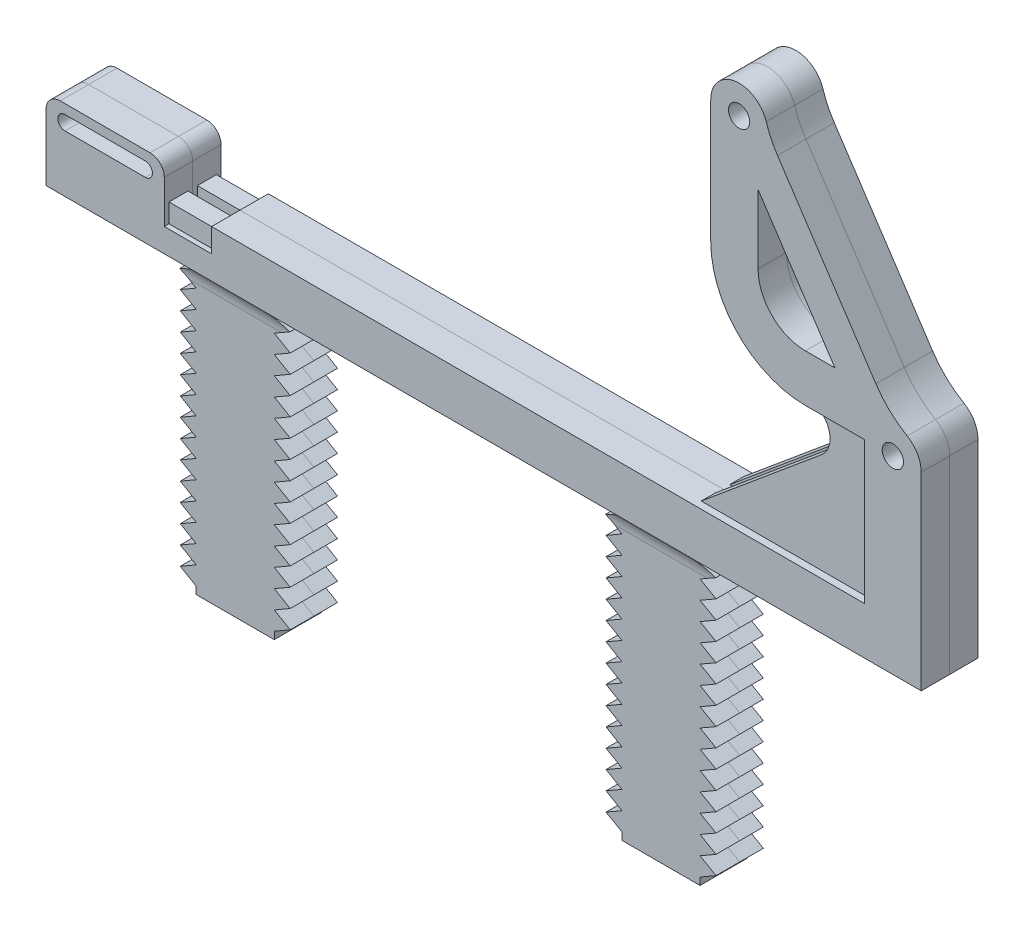
SolidWorks part; units mm, degrees
ref_plane "Front Plane" through (0, 0, 0) normal (0, 0, 1) x (1, 0, 0)
ref_plane "Top Plane" through (0, 0, 0) normal (0, 1, 0) x (1, 0, 0)
ref_plane "Right Plane" through (0, 0, 0) normal (1, 0, 0) x (0, 0, -1)
sketch "Sketch1" plane through (0, 0, 0) normal (0, 0, 1) x (1, 0, 0)
  line L0 (0, 0) -> (-32.49, 0) construction
  line L1 (-6, 0) -> (6, 0) construction
  line L2 (-6, 0) -> (-6, -40)
  line L3 (-6, -40) -> (6, -40)
  line L4 (6, 0) -> (6, -40)
  line L5 (-32.49, 0) -> (-32.49, 46) construction
  line L6 (-38.49, 46) -> (-38.49, 0)
  line L7 (-38.49, 0) -> (-6, 0)
  line L8 (-26.49, 46) -> (0, 6)
  line L9 (-28.49, 34.5311) -> (-12.2442, 10)
  line L10 (-12.2442, 10) -> (-28.49, 10)
  line L11 (-28.49, 10) -> (-28.49, 34.5311)
  circle A0 centre (0, 0) radius 2.25
  arc A1 (6, 0) -> (0, 6) centre (0, 0) ccw
  circle A2 centre (-32.49, 46) radius 2.25
  arc A3 (-26.49, 46) -> (-38.49, 46) centre (-32.49, 46) ccw
  dimension "D1" = 4.5
  dimension "D2" = 12
  dimension "D6" = 4.5
  dimension "D7" = 12
  dimension "D3" = 40
  dimension "D4" = 32.49
  dimension "D5" = 46
  dimension "D8" = 8
  dimension "D9" = 10
  dimension "D10" = 10
extrude "Boss-Extrude1" add sketch "Sketch1" along normal blind 6
sketch "Sketch2" plane through (0, 0, 0) normal (0, 0, 1) x (1, 0, 0)
  line L0 (-175, -26.5) -> (-158, -26.5) construction
  line L1 (6, -40) -> (-179, -40)
  line L2 (6, -40) -> (6, -30)
  line L3 (6, -30) -> (-154, -30)
  line L4 (-179, -40) -> (-179, -30)
  line L6 (-179, -30) -> (-179, -23)
  line L7 (-179, -23) -> (-154, -23)
  line L8 (-154, -30) -> (-154, -23)
  line L9 (-175, -25) -> (-158, -25)
  line L10 (-175, -28) -> (-158, -28)
  arc A0 (-175, -25) -> (-175, -28) centre (-175, -26.5) ccw
  arc A1 (-158, -28) -> (-158, -25) centre (-158, -26.5) ccw
  point P10 (-166.5, -26.5)
  point P16 (-154, -26.5)
  point P18 (-166.5, -23)
  dimension "D1" = 10
  dimension "D2" = 185
  dimension "D3" = 25
  dimension "D4" = 3
  dimension "D5" = 17
  dimension "D6" = 2
extrude "Boss-Extrude2" add sketch "Sketch2" along normal blind 6
fillet "Fillet1" radius 3 2 edges at (-179, -23, 3) (-154, -23, 3)
sketch "Sketch3" plane through (0, 0, 6) normal (0, 0, 1) x (1, 0, 0)
  line L1 (-6, 0) -> (-42, -30)
  line L2 (-6, -30) -> (-154, -30) construction
  line L3 (-42, -30) -> (-6, -30)
  line L4 (-6, 0) -> (-6, -30) construction
  line L5 (-6, 0) -> (-6, -30)
  dimension "D1" = 36
extrude "Boss-Extrude3" add sketch "Sketch3" along normal blind 3 from offset 4.5 offset against normal yes
sketch "Sketch4" plane through (-154, 0, 0) normal (1, 0, 0) x (0, 0, -1)
  line L0 (0, -40) -> (0, 0) construction
  line L1 (-6, -30) -> (0, -30)
  line L2 (-6, -30) -> (-6, -35)
  line L3 (-6, -35) -> (-5, -35)
  line L4 (0, -30) -> (0, -35)
  line L5 (-5, -34) -> (-1, -34) construction
  line L6 (-1, -31) -> (-1, -34)
  line L7 (-5, -31) -> (-1, -31)
  line L8 (-5, -31) -> (-5, -34)
  line L9 (-5, -34) -> (-5, -35)
  line L10 (-1, -34) -> (-1, -40)
  line L11 (-6, -40) -> (0, -40) construction
  line L12 (-6, -35) -> (0, -35) construction
  line L13 (0, -35) -> (0, -40)
  line L14 (0, -40) -> (-1, -40)
  dimension "D1" = 1
  dimension "D2" = 5
extrude "Cut-Extrude1" cut sketch "Sketch4" along normal blind 10
fillet "Fillet2" radius 20 1 edges at (-38.49, 0, 3)
fillet "Fillet3" radius 5 1 edges at (-6, 0, 3) tangent propagation no
fillet "Fillet4" radius 20 2 edges at (0, 6, 3) (-26.49, 46, 3)
fillet "Fillet5" radius 10 1 edges at (-28.49, 10, 3)
sketch "Sketch5" plane through (0, 0, 0) normal (0, 0, 1) x (1, 0, 0)
  line L0 (-179, -40) -> (6, -40) construction
  line L1 (-179, -40) -> (6, -40) construction
  line L2 (-50, -40) -> (-50, -69.654) construction
  line L3 (0, 0) -> (0, -70) construction
  line L4 (-119.6056, -70) -> (64.6682, -70) construction
  line L5 (-58.25, -40) -> (-61.625, -41.9486)
  line L6 (-58.25, -40) -> (-41.75, -40)
  line L8 (-58.25, -100) -> (-41.75, -100)
  line L9 (-41.75, -40) -> (-41.75, -90.6625) construction
  line L10 (-61.625, -41.9486) -> (-58.25, -43.8971)
  line L11 (-58.25, -43.8971) -> (-58.25, -40) construction
  line L12 (-58.25, -43.8971) -> (-58.25, -90.6625) construction
  line L13 (-61.625, -41.9486) -> (-61.625, -86.7031) construction
  line L14 (-58.25, -43.8971) -> (-61.625, -45.8457)
  line L15 (-61.625, -45.8457) -> (-58.25, -47.7942)
  line L16 (-58.25, -47.7942) -> (-61.625, -49.7428)
  line L17 (-61.625, -49.7428) -> (-58.25, -51.6913)
  line L18 (-58.25, -51.6913) -> (-61.625, -53.6399)
  line L19 (-61.625, -53.6399) -> (-58.25, -55.5885)
  line L20 (-58.25, -55.5885) -> (-61.625, -57.537)
  line L21 (-61.625, -57.537) -> (-58.25, -59.4856)
  line L22 (-58.25, -59.4856) -> (-61.625, -61.4341)
  line L23 (-61.625, -61.4341) -> (-58.25, -63.3827)
  line L24 (-58.25, -63.3827) -> (-61.625, -65.3312)
  line L25 (-61.625, -65.3312) -> (-58.25, -67.2798)
  line L26 (-58.25, -67.2798) -> (-61.625, -69.2284)
  line L27 (-61.625, -69.2284) -> (-58.25, -71.1769)
  line L28 (-58.25, -71.1769) -> (-61.625, -73.1255)
  line L29 (-61.625, -73.1255) -> (-58.25, -75.074)
  line L30 (-58.25, -75.074) -> (-61.625, -77.0226)
  line L31 (-61.625, -77.0226) -> (-58.25, -78.9711)
  line L32 (-58.25, -78.9711) -> (-61.625, -80.9197)
  line L33 (-61.625, -80.9197) -> (-58.25, -82.8683)
  line L34 (-58.25, -82.8683) -> (-61.625, -84.8168)
  line L35 (-61.625, -84.8168) -> (-58.25, -86.7654)
  line L36 (-58.25, -86.7654) -> (-61.625, -88.7139)
  line L37 (-61.625, -88.7139) -> (-58.25, -90.6625)
  line L38 (-58.25, -98.4567) -> (-58.25, -100)
  line L39 (-41.75, -98.4567) -> (-41.75, -100)
  line L40 (-38.375, -88.7139) -> (-41.75, -90.6625)
  line L41 (-41.75, -86.7654) -> (-38.375, -88.7139)
  line L42 (-38.375, -84.8168) -> (-41.75, -86.7654)
  line L43 (-41.75, -82.8683) -> (-38.375, -84.8168)
  line L44 (-38.375, -80.9197) -> (-41.75, -82.8683)
  line L45 (-41.75, -78.9711) -> (-38.375, -80.9197)
  line L46 (-38.375, -77.0226) -> (-41.75, -78.9711)
  line L47 (-41.75, -75.074) -> (-38.375, -77.0226)
  line L48 (-38.375, -73.1255) -> (-41.75, -75.074)
  line L49 (-41.75, -71.1769) -> (-38.375, -73.1255)
  line L50 (-38.375, -69.2284) -> (-41.75, -71.1769)
  line L51 (-41.75, -67.2798) -> (-38.375, -69.2284)
  line L52 (-38.375, -65.3312) -> (-41.75, -67.2798)
  line L53 (-41.75, -63.3827) -> (-38.375, -65.3312)
  line L54 (-38.375, -61.4341) -> (-41.75, -63.3827)
  line L55 (-41.75, -59.4856) -> (-38.375, -61.4341)
  line L56 (-38.375, -57.537) -> (-41.75, -59.4856)
  line L57 (-41.75, -55.5885) -> (-38.375, -57.537)
  line L58 (-38.375, -53.6399) -> (-41.75, -55.5885)
  line L59 (-41.75, -51.6913) -> (-38.375, -53.6399)
  line L60 (-38.375, -49.7428) -> (-41.75, -51.6913)
  line L61 (-41.75, -47.7942) -> (-38.375, -49.7428)
  line L62 (-38.375, -45.8457) -> (-41.75, -47.7942)
  line L63 (-41.75, -43.8971) -> (-38.375, -45.8457)
  line L64 (-38.375, -41.9486) -> (-41.75, -43.8971)
  line L65 (-41.75, -40) -> (-38.375, -41.9486)
  line L66 (-58.25, -90.6625) -> (-61.625, -92.611)
  line L67 (-61.625, -92.611) -> (-58.25, -94.5596)
  line L68 (-41.75, -90.6625) -> (-38.375, -92.611)
  line L69 (-38.375, -92.611) -> (-41.75, -94.5596)
  line L70 (-58.25, -94.5596) -> (-61.625, -96.5082)
  line L71 (-61.625, -96.5082) -> (-58.25, -98.4567)
  line L72 (-41.75, -94.5596) -> (-38.375, -96.5082)
  line L73 (-38.375, -96.5082) -> (-41.75, -98.4567)
  line L74 (-41.75, -98.4567) -> (-41.75, -100) construction
  point P13 (-50, -100)
  dimension "D1" = 50
  dimension "D2" = 30
  dimension "D3" = 8.25
  dimension "D4" = 3.375
  dimension "D5" = 13
  dimension "D6" = 30
  dimension "D7" = 3
extrude "Boss-Extrude5" add sketch "Sketch5" along normal blind 5
pattern_linear "LPattern1" count 2 spacing 90 along (-1, 0, 0) of "Boss-Extrude5"
fillet "Fillet6" radius 5 2 edges at (-50, -40, 5) (-140, -40, 5)
mirror "Mirror1" about plane through (0, 0, 0) normal (0, 0, 1) of bodies 107
